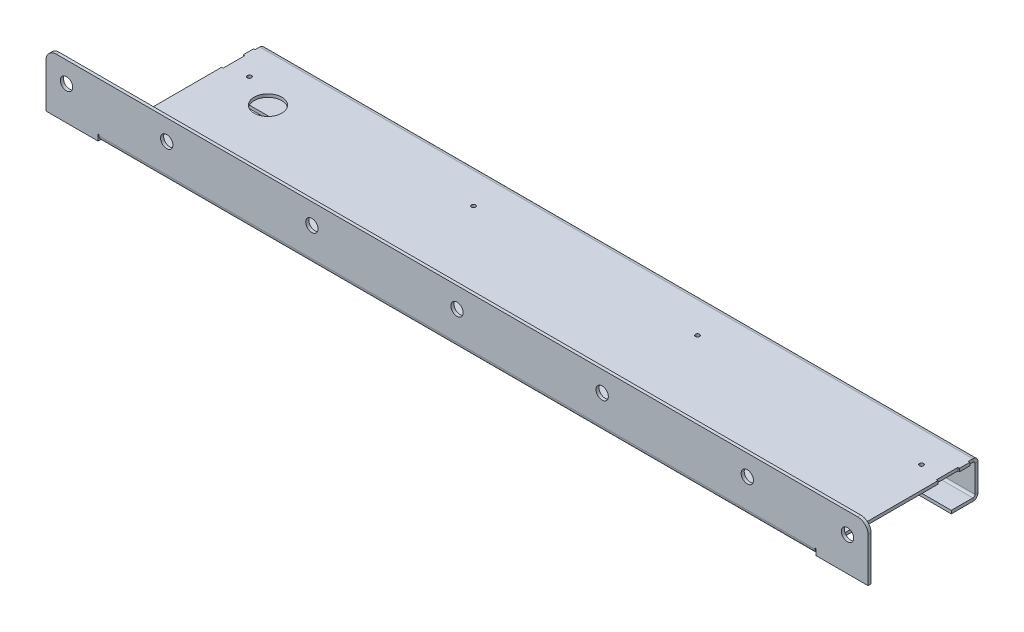
SolidWorks part; units mm, degrees
note: The reader was unsure of these and kept them because the rebuilt part matched: thickness of "Base-Flange1", "Edge-Flange1", "Edge-Flange2", "Edge-Flange3", "Sheet-Metal5", "Sheet-Metal6", "Sheet-Metal7", "Sheet-Metal8", "Sheet-Metal11", "Sheet-Metal12", "Sheet-Metal13", "Sheet-Metal15", "Sheet-Metal16", "Sheet-Metal17", "Sheet-Metal18", "Sheet-Metal19"; flange length of "Edge-Flange1", "Edge-Flange2", "Edge-Flange3".
material "3.0 mm SS316 2B/2B"
ref_plane "Front Plane" through (0, 0, 0) normal (0, 0, 1) x (1, 0, 0)
ref_plane "Top Plane" through (0, 0, 0) normal (0, 1, 0) x (1, 0, 0)
ref_plane "Right Plane" through (0, 0, 0) normal (1, 0, 0) x (0, 0, -1)
sketch "Sketch2" plane through (0, 0, 0) normal (0, 0, 1) x (1, 0, 0)
  line L0 (400, 26.5) -> (-400, -26.5) construction
  line L1 (400, 26.5) -> (-400, 26.5)
  line L2 (400, 26.5) -> (400, -26.5)
  line L3 (400, -26.5) -> (-400, -26.5)
  line L4 (-400, 26.5) -> (-400, -26.5)
  line L5 (-400, 26.5) -> (400, -26.5) construction
  dimension "D1" = 800
  dimension "D2" = 53
base flange "Base-Flange1" sketch "Sketch2" thickness 3 reverse thickness direction no parameters "D1"=2
edge flange "Edge-Flange1" sketch "Sketch9" flange angle 90 flange length 160 flange position material inside bend radius 2 thickness 3 relief rectangular parameters "D1"=5, "D6"=10
sketch "Sketch9" plane through (0, -26.5, -3) normal (0, 1, 0) x (1, 0, 0)
  line L0 (-348.5, 16.5) -> (-347, 16.5)
  line L1 (400, 0) -> (-400, 0) construction
  line L2 (348.5, 37.5) -> (348.5, 116.5)
  line L3 (-347, 157) -> (347, 157)
  line L4 (-400, -3) -> (400, -3) construction
  line L5 (348.5, 0) -> (-348.5, 0)
  line L6 (0, 0) -> (0, 157) construction
  line L7 (347, 147.5) -> (347, 157)
  line L8 (-348.5, 0) -> (-348.5, 16.5)
  line L9 (-348.5, 137.5) -> (-348.5, 147.5)
  line L10 (-347, 16.5) -> (-347, 37.5)
  line L11 (-347, 37.5) -> (-348.5, 37.5)
  line L12 (-348.5, 137.5) -> (-347, 137.5)
  line L13 (-347, 137.5) -> (-347, 116.5)
  line L14 (-347, 116.5) -> (-348.5, 116.5)
  line L15 (-348.5, 147.5) -> (-347, 147.5)
  line L16 (-347, 147.5) -> (-347, 157)
  line L17 (-348.5, 37.5) -> (-348.5, 116.5)
  line L18 (348.5, 147.5) -> (347, 147.5)
  line L19 (347, 116.5) -> (348.5, 116.5)
  line L20 (347, 137.5) -> (347, 116.5)
  line L21 (348.5, 137.5) -> (347, 137.5)
  line L22 (347, 37.5) -> (348.5, 37.5)
  line L23 (347, 16.5) -> (347, 37.5)
  line L24 (348.5, 137.5) -> (348.5, 147.5)
  line L25 (348.5, 0) -> (348.5, 16.5)
  line L26 (348.5, 16.5) -> (347, 16.5)
  line L27 (-348.5, 77) -> (348.5, 77) construction
  line L28 (400, -3) -> (-400, -3) construction
  dimension "D1" = 694
  dimension "D2" = 160
  dimension "D3" = 100
  dimension "D4" = 21
  dimension "D5" = 10
  dimension "D6" = 1.5
  dimension "D7" = 80
bend "EdgeBend1" bend radius 2 bend angle 90 parameters "D5"=1
edge flange "Edge-Flange2" sketch "Sketch12" flange angle 90 flange length 36 flange position material inside bend radius 2 thickness 3 relief rectangular parameters "D1"=5, "D6"=10
sketch "Sketch12" plane through (0, -26.5, -160) normal (0, 0, 1) x (-1, 0, 0)
  line L0 (0, 0) -> (0, 33) construction
  line L1 (347, 0) -> (-347, 0) construction
  line L2 (-347, 0) -> (-347, 33)
  line L3 (-347, 33) -> (347, 33)
  line L4 (347, 0) -> (347, 33)
  line L5 (347, 0) -> (-347, 0)
  line L6 (-347, 0) -> (347, 0) construction
bend "EdgeBend2" bend radius 2 bend angle 90 parameters "D5"=2
edge flange "Edge-Flange3" sketch "Sketch15" flange angle 90 flange length 26 flange position material inside bend radius 2 thickness 3 relief rectangular parameters "D1"=5, "D6"=10
sketch "Sketch15" plane through (0, -59.5, -157) normal (0, 1, 0) x (-1, 0, 0)
  line L1 (347, 0) -> (-347, 0) construction
  line L2 (-347, 0) -> (-347, 23)
  line L3 (-347, 23) -> (347, 23)
  line L4 (347, 23) -> (347, 0)
  line L5 (347, 0) -> (-347, 0)
bend "EdgeBend3" bend radius 2 bend angle 90 parameters "D5"=3
fillet "Fillet1" radius 10 2 edges at (-400, 26.5, -1.5) (400, 26.5, -1.5)
sketch "Sketch19" plane through (0, 0, -160) normal (0, 0, -1) x (-1, 0, 0)
  line L0 (-347, -54.5) -> (-347, -28.5) construction
  line L1 (-286.5914, -39.5) -> (-289.7957, -33.95)
  line L2 (-289.7957, -33.95) -> (-296.2043, -33.95)
  line L3 (-296.2043, -33.95) -> (-299.4086, -39.5)
  line L4 (-299.4086, -39.5) -> (-296.2043, -45.05)
  line L5 (-296.2043, -45.05) -> (-289.7957, -45.05)
  line L6 (-289.7957, -45.05) -> (-286.5914, -39.5)
  line L7 (347, -59.5) -> (-347, -59.5) construction
  circle A0 centre (-293, -39.5) radius 5.55 construction
  dimension "D1" = 11.1
  dimension "D2" = 54
  dimension "D3" = 20
extrude "Cut-Extrude2" cut sketch "Sketch19" against normal up to surface (3 mm away) normal cut yes up to face at (0, -41.5, -157)
pattern_linear "LPattern1" count 4 spacing 195.3333 along (-1, 0, 0) of "Cut-Extrude2"
sketch "Sketch20" plane through (0, 0, -3) normal (0, 0, -1) x (-1, 0, 0)
  line L0 (0, 26.5) -> (0, -59.5) construction
  line L1 (347, -59.5) -> (-347, -59.5) construction
  line L2 (-390, 26.5) -> (390, 26.5) construction
  line L3 (-400, -26.5) -> (-400, 16.5) construction
  circle A0 centre (-380, 6.5) radius 6
  circle A1 centre (380, 6.5) radius 6
  dimension "D1" = 12
  dimension "D2" = 20
  dimension "D3" = 20
extrude "Cut-Extrude3" cut sketch "Sketch20" against normal up to surface (3 mm away) normal cut yes up to face at (0, -10.0898, 0)
sketch "Sketch21" plane through (0, 0, -3) normal (0, 0, -1) x (-1, 0, 0)
  line L0 (-282.5, 6.5) -> (-380, 6.5) construction
  circle A0 centre (-282.5, 6.5) radius 6
  circle A1 centre (-380, 6.5) radius 6 construction
  dimension "D1" = 97.5
extrude "Cut-Extrude4" cut sketch "Sketch21" against normal up to surface (3 mm away) contours A0 normal cut yes up to face at (-386, 6.5, 0)
pattern_linear "LPattern2" count 5 spacing 141.25 along (-1, 0, 0) of "Cut-Extrude4"
sketch "Sketch22" plane through (0, -23.5, 0) normal (0, 1, 0) x (1, 0, 0)
  line L0 (390, 0) -> (-390, 0) construction
  line L1 (-347, 160) -> (347, 160) construction
  line L2 (-327, 16) -> (-327, 125) construction
  line L3 (-347, 155) -> (-347, 150.5) construction
  circle A0 centre (-327, 16) radius 2
  circle A1 centre (-327, 39) radius 2
  circle A2 centre (-327, 125) radius 2
  dimension "D1" = 35
  dimension "D4" = 4
  dimension "D2" = 86
  dimension "D3" = 16
  dimension "D5" = 20
extrude "Cut-Extrude5" cut sketch "Sketch22" against normal up to surface (3 mm away) normal cut yes up to face at (0, -26.5, -91.75)
pattern_linear "LPattern3" count 4 spacing 218 along (1, 0, 0) of "Cut-Extrude5"
sketch "Sketch23" plane through (0, -23.5, 0) normal (0, 1, 0) x (1, 0, 0)
  line L2 (-347, 155) -> (-347, 150.5) construction
  line L3 (-347, 160) -> (347, 160) construction
  circle A0 centre (-294, 110) radius 13.5
  dimension "D3" = 27
  dimension "D1" = 50
  dimension "D2" = 53
extrude "Cut-Extrude6" cut sketch "Sketch23" against normal blind 10
sketch "Bend-Lines1" [suppressed] plane through (0, 0, 0) normal (0, 1, 0) x (1, 0, 0)
sketch "Bounding-Box1" [suppressed] plane through (0, 0, 0) normal (0, 1, 0) x (1, 0, 0)
sheet metal parameters "Sheet-Metal5" thickness 3 parameters "D1"=3, "D7"=5
flat pattern "Flat-Pattern5" [suppressed]
sketch "Bend-Lines2" plane through (0, 0, 0) normal (0, 1, 0) x (1, 0, 0)
sketch3d "Bounding-Box2" [suppressed]
  line L0 (-393, -25, 0) -> (393, -25, 0) construction
  line L1 (-393, 25, 0) -> (393, 25, 0) construction
  line L2 (-393, -25, 0) -> (-393, 25, 0) construction
  line L3 (393, -25, 0) -> (393, 25, 0) construction
sheet metal parameters "Sheet-Metal6" thickness 3 parameters "D1"=3, "D7"=5
flat pattern "Flat-Pattern5"
sketch "Bend-Lines2" plane through (0, 0, 0) normal (0, 0, 1) x (1, 0, 0)
  line L0 (-344, -23) -> (344, -23) construction
  line L1 (-344, -23) -> (344, -23) construction
sketch3d "Bounding-Box2" [suppressed]
  line L0 (-393, -181, 0) -> (393, -181, 0) construction
  line L1 (-393, 25, 0) -> (393, 25, 0) construction
  line L2 (-393, -181, 0) -> (-393, 25, 0) construction
  line L3 (393, -181, 0) -> (393, 25, 0) construction
bend of the flat pattern "Flatten-<EdgeBend1>1"
sheet metal parameters "Sheet-Metal7" thickness 3 parameters "D1"=3, "D7"=5
flat pattern "Flat-Pattern5"
sketch "Bend-Lines2" plane through (0, 0, 0) normal (0, 0, 1) x (1, 0, 0)
  line L0 (-343, -179) -> (343, -179) construction
  line L1 (-344, -23) -> (344, -23) construction
  line L2 (-343, -179) -> (343, -179) construction
  line L3 (-344, -23) -> (344, -23) construction
sketch3d "Bounding-Box2" [suppressed]
  line L0 (-393, -213, 0) -> (393, -213, 0) construction
  line L1 (-393, 25, 0) -> (393, 25, 0) construction
  line L2 (-393, -213, 0) -> (-393, 25, 0) construction
  line L3 (393, -213, 0) -> (393, 25, 0) construction
bend of the flat pattern "Flatten-<EdgeBend1>1"
bend of the flat pattern "Flatten-<EdgeBend2>1"
sheet metal parameters "Sheet-Metal8" thickness 3 parameters "D1"=3, "D7"=5
flat pattern "Flat-Pattern5"
sketch "Bend-Lines2" plane through (0, 0, 0) normal (0, 0, 1) x (1, 0, 0)
  line L0 (-343, -211) -> (343, -211) construction
  line L1 (-343, -179) -> (343, -179) construction
  line L2 (-344, -23) -> (344, -23) construction
  line L3 (-343, -211) -> (343, -211) construction
  line L4 (-343, -179) -> (343, -179) construction
  line L5 (-344, -23) -> (344, -23) construction
sketch3d "Bounding-Box2" [suppressed]
  line L0 (-393, -235, 0) -> (393, -235, 0) construction
  line L1 (-393, 25, 0) -> (393, 25, 0) construction
  line L2 (-393, -235, 0) -> (-393, 25, 0) construction
  line L3 (393, -235, 0) -> (393, 25, 0) construction
bend of the flat pattern "Flatten-<EdgeBend1>1"
bend of the flat pattern "Flatten-<EdgeBend2>1"
bend of the flat pattern "Flatten-<EdgeBend3>1"
sheet metal parameters "Sheet-Metal11" thickness 3 parameters "D1"=3, "D7"=5
flat pattern "Flat-Pattern5"
sketch "Bend-Lines2" plane through (0, 0, 0) normal (0, 0, 1) x (1, 0, 0)
  line L0 (-343, -211) -> (343, -211) construction
  line L1 (-343, -179) -> (343, -179) construction
  line L2 (-344, -23) -> (344, -23) construction
  line L3 (-343, -211) -> (343, -211) construction
  line L4 (-343, -179) -> (343, -179) construction
  line L5 (-344, -23) -> (344, -23) construction
sketch3d "Bounding-Box2" [suppressed]
  line L0 (-393, -235, 0) -> (393, -235, 0) construction
  line L1 (-393, 25, 0) -> (393, 25, 0) construction
  line L2 (-393, -235, 0) -> (-393, 25, 0) construction
  line L3 (393, -235, 0) -> (393, 25, 0) construction
bend of the flat pattern "Flatten-<EdgeBend1>1"
bend of the flat pattern "Flatten-<EdgeBend2>1"
bend of the flat pattern "Flatten-<EdgeBend3>1"
sheet metal parameters "Sheet-Metal12" thickness 3 parameters "D1"=3, "D7"=5
flat pattern "Flat-Pattern5"
sketch "Bend-Lines2" plane through (0, 0, 0) normal (0, 0, 1) x (1, 0, 0)
  line L0 (-343, -211) -> (343, -211) construction
  line L1 (-343, -179) -> (343, -179) construction
  line L2 (-344, -23) -> (344, -23) construction
  line L3 (-343, -211) -> (343, -211) construction
  line L4 (-343, -179) -> (343, -179) construction
  line L5 (-344, -23) -> (344, -23) construction
sketch3d "Bounding-Box2" [suppressed]
  line L0 (-393, -235, 0) -> (393, -235, 0) construction
  line L1 (-393, 25, 0) -> (393, 25, 0) construction
  line L2 (-393, -235, 0) -> (-393, 25, 0) construction
  line L3 (393, -235, 0) -> (393, 25, 0) construction
bend of the flat pattern "Flatten-<EdgeBend1>1"
bend of the flat pattern "Flatten-<EdgeBend2>1"
bend of the flat pattern "Flatten-<EdgeBend3>1"
sheet metal parameters "Sheet-Metal13" thickness 3 parameters "D1"=3, "D7"=5
flat pattern "Flat-Pattern5"
sketch "Bend-Lines2" plane through (0, 0, 0) normal (0, 0, 1) x (1, 0, 0)
  line L0 (-343, -211) -> (343, -211) construction
  line L1 (-343, -179) -> (343, -179) construction
  line L2 (-344, -23) -> (344, -23) construction
  line L3 (-343, -211) -> (343, -211) construction
  line L4 (-343, -179) -> (343, -179) construction
  line L5 (-344, -23) -> (344, -23) construction
sketch3d "Bounding-Box2" [suppressed]
  line L0 (-393, -235, 0) -> (393, -235, 0) construction
  line L1 (-393, 25, 0) -> (393, 25, 0) construction
  line L2 (-393, -235, 0) -> (-393, 25, 0) construction
  line L3 (393, -235, 0) -> (393, 25, 0) construction
bend of the flat pattern "Flatten-<EdgeBend3>1"
bend of the flat pattern "Flatten-<EdgeBend2>1"
bend of the flat pattern "Flatten-<EdgeBend1>1"
sheet metal parameters "Sheet-Metal15" thickness 3 parameters "D1"=3, "D7"=5
flat pattern "Flat-Pattern5"
sketch "Bend-Lines2" plane through (0, 0, 0) normal (0, 0, 1) x (1, 0, 0)
  line L0 (-343, -211) -> (343, -211) construction
  line L1 (-343, -179) -> (343, -179) construction
  line L2 (-344, -23) -> (344, -23) construction
  line L3 (-343, -211) -> (343, -211) construction
  line L4 (-343, -179) -> (343, -179) construction
  line L5 (-344, -23) -> (344, -23) construction
sketch3d "Bounding-Box2" [suppressed]
  line L0 (-393, -235, 0) -> (393, -235, 0) construction
  line L1 (-393, 25, 0) -> (393, 25, 0) construction
  line L2 (-393, -235, 0) -> (-393, 25, 0) construction
  line L3 (393, -235, 0) -> (393, 25, 0) construction
bend of the flat pattern "Flatten-<EdgeBend3>1"
bend of the flat pattern "Flatten-<EdgeBend2>1"
bend of the flat pattern "Flatten-<EdgeBend1>1"
sheet metal parameters "Sheet-Metal16" thickness 3 parameters "D1"=3, "D7"=5
flat pattern "Flat-Pattern5"
sketch "Bend-Lines2" plane through (0, 0, 0) normal (0, 0, 1) x (1, 0, 0)
  line L0 (-343, -211) -> (343, -211) construction
  line L1 (-343, -179) -> (343, -179) construction
  line L2 (-344, -23) -> (344, -23) construction
  line L3 (-343, -211) -> (343, -211) construction
  line L4 (-343, -179) -> (343, -179) construction
  line L5 (-344, -23) -> (344, -23) construction
sketch3d "Bounding-Box2" [suppressed]
  line L0 (-393, -235, 0) -> (393, -235, 0) construction
  line L1 (-393, 25, 0) -> (393, 25, 0) construction
  line L2 (-393, -235, 0) -> (-393, 25, 0) construction
  line L3 (393, -235, 0) -> (393, 25, 0) construction
bend of the flat pattern "Flatten-<EdgeBend3>1"
bend of the flat pattern "Flatten-<EdgeBend2>1"
bend of the flat pattern "Flatten-<EdgeBend1>1"
sheet metal parameters "Sheet-Metal17" thickness 3 parameters "D1"=3, "D7"=5
flat pattern "Flat-Pattern5"
sketch "Bend-Lines2" plane through (0, 0, 0) normal (0, 0, 1) x (1, 0, 0)
  line L0 (-343, -211) -> (343, -211) construction
  line L1 (-343, -179) -> (343, -179) construction
  line L2 (-344, -23) -> (344, -23) construction
  line L3 (-343, -211) -> (343, -211) construction
  line L4 (-343, -179) -> (343, -179) construction
  line L5 (-344, -23) -> (344, -23) construction
sketch3d "Bounding-Box2" [suppressed]
  line L0 (-393, -235, 0) -> (393, -235, 0) construction
  line L1 (-393, 25, 0) -> (393, 25, 0) construction
  line L2 (-393, -235, 0) -> (-393, 25, 0) construction
  line L3 (393, -235, 0) -> (393, 25, 0) construction
bend of the flat pattern "Flatten-<EdgeBend1>1"
bend of the flat pattern "Flatten-<EdgeBend2>1"
bend of the flat pattern "Flatten-<EdgeBend3>1"
sheet metal parameters "Sheet-Metal18" thickness 3 parameters "D1"=3, "D7"=5
flat pattern "Flat-Pattern5"
sketch "Bend-Lines2" plane through (0, 0, 0) normal (0, 0, 1) x (1, 0, 0)
  line L0 (-343, -211) -> (343, -211) construction
  line L1 (-343, -179) -> (343, -179) construction
  line L2 (-344, -23) -> (344, -23) construction
  line L3 (-343, -211) -> (343, -211) construction
  line L4 (-343, -179) -> (343, -179) construction
  line L5 (-344, -23) -> (344, -23) construction
sketch3d "Bounding-Box2" [suppressed]
  line L0 (-393, -235, 0) -> (393, -235, 0) construction
  line L1 (-393, 25, 0) -> (393, 25, 0) construction
  line L2 (-393, -235, 0) -> (-393, 25, 0) construction
  line L3 (393, -235, 0) -> (393, 25, 0) construction
bend of the flat pattern "Flatten-<EdgeBend1>1"
bend of the flat pattern "Flatten-<EdgeBend2>1"
bend of the flat pattern "Flatten-<EdgeBend3>1"
sheet metal parameters "Sheet-Metal19" thickness 3 parameters "D1"=3, "D7"=5
flat pattern "Flat-Pattern5"
sketch "Bend-Lines2" plane through (0, 0, 0) normal (0, 0, 1) x (1, 0, 0)
  line L0 (-347, -207.5) -> (347, -207.5) construction
  line L1 (-347, -177.5) -> (347, -177.5) construction
  line L2 (-348.5, -23.5) -> (348.5, -23.5) construction
  line L3 (-347, -207.5) -> (347, -207.5) construction
  line L4 (-347, -177.5) -> (347, -177.5) construction
  line L5 (-348.5, -23.5) -> (348.5, -23.5) construction
sketch3d "Bounding-Box2" [suppressed]
  line L0 (-400, -230.5, 0) -> (400, -230.5, 0) construction
  line L1 (-400, 26.5, 0) -> (400, 26.5, 0) construction
  line L2 (-400, -230.5, 0) -> (-400, 26.5, 0) construction
  line L3 (400, -230.5, 0) -> (400, 26.5, 0) construction
bend of the flat pattern "Flatten-<EdgeBend1>1"
bend of the flat pattern "Flatten-<EdgeBend2>1"
bend of the flat pattern "Flatten-<EdgeBend3>1"
